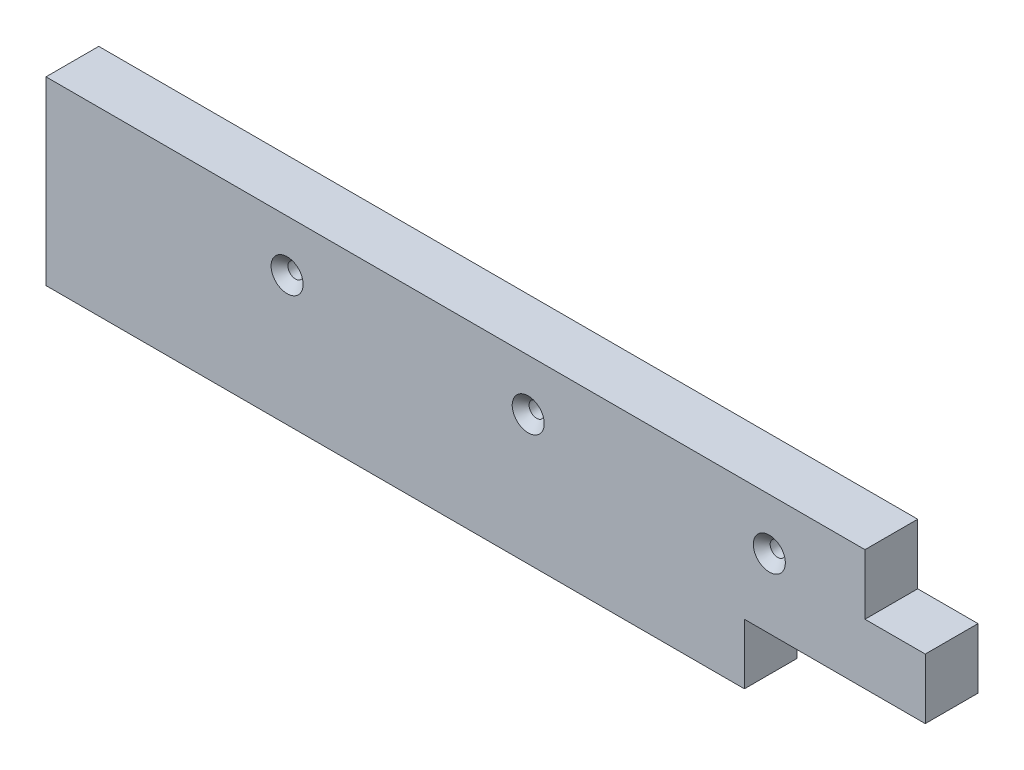
SolidWorks part; units mm, degrees
ref_plane "Front Plane" through (0, 0, 0) normal (0, 0, 1) x (1, 0, 0)
ref_plane "Top Plane" through (0, 0, 0) normal (0, 1, 0) x (1, 0, 0)
ref_plane "Right Plane" through (0, 0, 0) normal (1, 0, 0) x (0, 0, -1)
sketch "Sketch1" plane through (0, 0, 0) normal (0, 1, 0) x (1, 0, 0)
  line L1 (-185.2521, -11.1125) -> (185.2521, -11.1125)
  line L2 (-185.2521, -11.1125) -> (-185.2521, 11.1125)
  line L3 (-185.2521, 11.1125) -> (185.2521, 11.1125)
  line L4 (185.2521, -11.1125) -> (185.2521, 11.1125)
  line L5 (-185.2521, -11.1125) -> (185.2521, 11.1125) construction
  line L6 (-185.2521, 11.1125) -> (185.2521, -11.1125) construction
  point P0 (0, 0)
extrude "Boss-Extrude1" add sketch "Sketch1" along normal mid plane 76.2 contours L1 L4 L3 L2
sketch "Sketch3" plane through (0, 0, 11.1125) normal (0, 0, 1) x (1, 0, 0)
  line L1 (185.2521, 38.1) -> (159.8521, 38.1)
  line L2 (185.2521, 38.1) -> (185.2521, 12.7)
  line L3 (185.2521, 12.7) -> (159.8521, 12.7)
  line L4 (159.8521, 38.1) -> (159.8521, 12.7)
  line L5 (109.0521, -12.7) -> (185.2521, -12.7)
  line L6 (109.0521, -12.7) -> (109.0521, -38.1)
  line L7 (109.0521, -38.1) -> (185.2521, -38.1)
  line L8 (185.2521, -12.7) -> (185.2521, -38.1)
  dimension "D1" = 76.2
  dimension "D2" = 25.4
  dimension "D3" = 25.4
hole_wizard "CSK for M6 Hex Socket Countersunk Head Screw6" positions "Sketch21" profile "Sketch20" countersink size "M6" standard "Lanco STD" end condition through all
sketch "Sketch21" plane through (0, 0, 11.1125) normal (0, 0, 1) x (1, 0, 0)
  point P0 (-83.6521, 16.5075)
  point P8 (17.9479, 16.5075)
  point P11 (119.5479, 16.5075)
sketch "Sketch20" plane through (-83.6521, 16.5075, 11.1125) normal (1, 0, 0) x (0, -1, 0)
  line L0 (0, 0) -> (0, 22.225)
  line L1 (0, 22.225) -> (3.2, 22.225)
  line L2 (3.2, 22.225) -> (3.2, 3.55)
  line L3 (3.2, 3.55) -> (6.75, 0)
  line L5 (6.75, 0) -> (0, 0)
  line L6 (-3.2, 3.55) -> (-6.75, 0) construction
  line L11 (0, -6.35) -> (0, 107.95) construction
  dimension "Thru Hole Dia." = 6.4
  dimension "Thru Hole Depth" = 22.225
  dimension "Near C'Sink Dia." = 13.5
  dimension "Near C'Sink Angle" = 90
extrude "Cut-Extrude1" cut sketch "Sketch3" against normal through all
